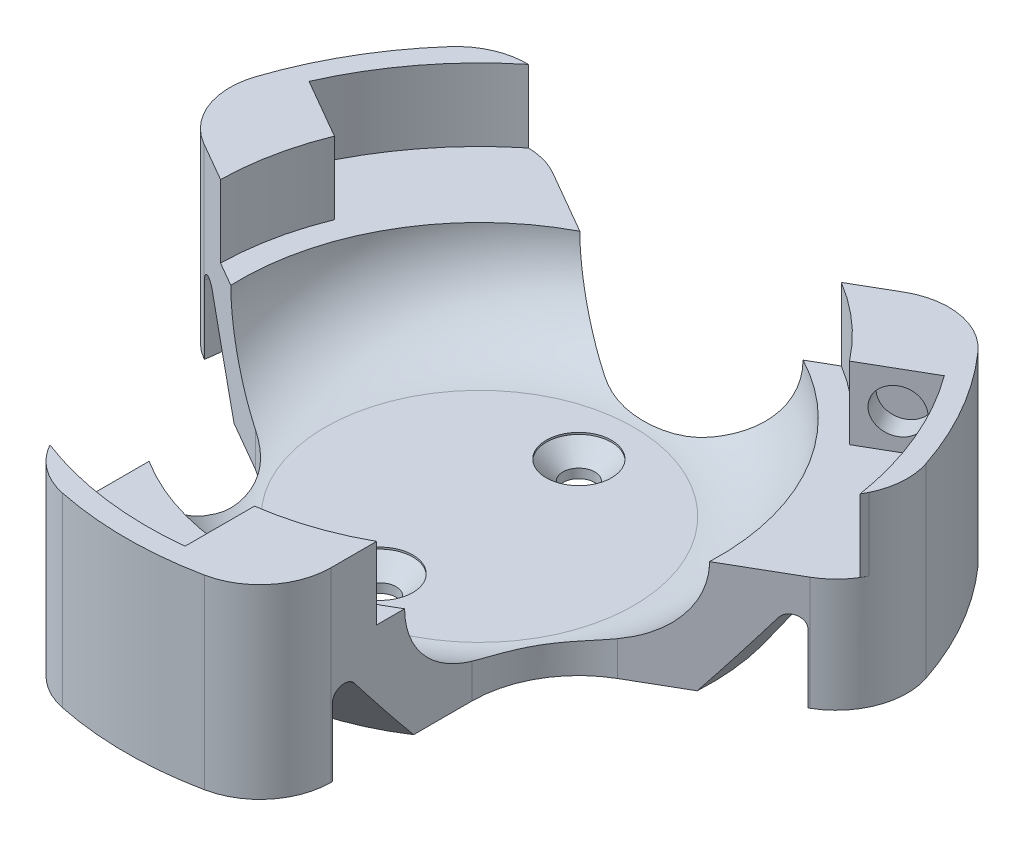
SolidWorks part; units mm, degrees
ref_plane "Front Plane" through (0, 0, 0) normal (0, 0, 1) x (1, 0, 0)
ref_plane "Top Plane" through (0, 0, 0) normal (0, 1, 0) x (1, 0, 0)
ref_plane "Right Plane" through (0, 0, 0) normal (1, 0, 0) x (0, 0, -1)
sketch "Sketch1" plane through (0, 0, 0) normal (0, 1, 0) x (1, 0, 0)
  line L0 (-56, 14) -> (-56, 42)
  line L1 (-28, 14) -> (-28, 42)
  line L3 (-28, 14) -> (-28, 42)
  line L4 (28, 14) -> (28, 42)
  line L5 (28, 14) -> (28, 42)
  line L7 (56, 14) -> (56, 42)
  line L8 (0, 14) -> (0, 42)
  line L9 (56, 14) -> (56, 42)
  line L10 (-56, 42) -> (-56, 70)
  line L11 (-56, 70) -> (-28, 70)
  line L12 (-28, 42) -> (-28, 70)
  line L13 (-28, 42) -> (-28, 70)
  line L15 (0, 70) -> (28, 70)
  line L16 (28, 42) -> (28, 70)
  line L17 (28, 42) -> (28, 70)
  line L18 (28, 70) -> (56, 70)
  line L19 (56, 42) -> (56, 70)
  line L20 (-28, 70) -> (0, 70)
  line L21 (56, 42) -> (56, 70)
  line L23 (0, 42) -> (0, 70)
  line L24 (-56, -14) -> (-56, 14)
  line L25 (-28, -14) -> (-28, 14)
  line L27 (-28, -14) -> (-28, 14)
  line L28 (28, -14) -> (28, 14)
  line L29 (28, -14) -> (28, 14)
  line L31 (56, -14) -> (56, 14)
  line L32 (0, -14) -> (0, 14)
  line L33 (56, -14) -> (56, 14)
  line L34 (-56, 14) -> (-56, 42)
  line L35 (-56, 42) -> (-28, 42)
  line L36 (-28, 14) -> (-28, 42)
  line L37 (-28, 14) -> (-28, 42)
  line L38 (0, 14) -> (0, 42)
  line L39 (0, 42) -> (28, 42)
  line L40 (28, 14) -> (28, 42)
  line L41 (28, 14) -> (28, 42)
  line L42 (28, 42) -> (56, 42)
  line L43 (56, 14) -> (56, 42)
  line L44 (-28, 42) -> (0, 42)
  line L45 (56, 14) -> (56, 42)
  line L46 (0, 14) -> (0, 42)
  line L47 (0, 14) -> (0, 42)
  line L48 (28, -42) -> (56, -42)
  line L49 (0, -42) -> (28, -42)
  line L51 (0, -14) -> (28, -14)
  line L52 (28, -42) -> (28, -14)
  line L53 (28, -42) -> (28, -14)
  line L54 (-28, -42) -> (0, -42)
  line L55 (56, -42) -> (56, -14)
  line L56 (-56, -42) -> (-28, -42)
  line L57 (56, -42) -> (56, -14)
  line L58 (-56, -42) -> (-56, -14)
  line L59 (-56, -14) -> (-28, -14)
  line L60 (28, -14) -> (56, -14)
  line L61 (0, -14) -> (28, -14)
  line L62 (0, -14) -> (0, 14)
  line L63 (0, 14) -> (28, 14)
  line L64 (28, -14) -> (28, 14)
  line L65 (28, -14) -> (28, 14)
  line L66 (28, 14) -> (56, 14)
  line L67 (56, -14) -> (56, 14)
  line L68 (-28, -42) -> (-28, -14)
  line L69 (56, -14) -> (56, 14)
  line L70 (-28, -42) -> (-28, -14)
  line L72 (84, 14) -> (84, 42)
  line L81 (0, -42) -> (0, -14)
  line L82 (-28, -14) -> (0, -14)
  line L83 (-56, -14) -> (-28, -14)
  line L84 (-56, -14) -> (-56, 14)
  line L85 (-56, 14) -> (-28, 14)
  line L86 (-28, -14) -> (-28, 14)
  line L87 (-28, -14) -> (-28, 14)
  line L88 (-28, 14) -> (0, 14)
  line L89 (0, -14) -> (0, 14)
  line L90 (0, -14) -> (0, 14)
  line L92 (0, -42) -> (0, -14)
  line L93 (0, -14) -> (0, 14)
  line L94 (0, 14) -> (0, 42)
  line L95 (0, 42) -> (0, 70)
  dimension "D3" = 3
  dimension "D4" = 2
  dimension "D5" = 3
  dimension "D6" = 2
sketch "Sketch2" plane through (0, 0, 0) normal (0, 1, 0) x (1, 0, 0)
  circle A0 centre (0, 0) radius 33.75
  circle A1 centre (0, 0) radius 49.75
  dimension "D1" = 67.5
  dimension "D2" = 16
extrude "Boss-Extrude1" add sketch "Sketch2" along normal blind 12
sketch "Sketch4" plane through (0, 0, 0) normal (0, 0, 1) x (1, 0, 0)
  line L2 (49.75, 12) -> (-49.75, 12) construction
  line L3 (-49.75, 0) -> (49.75, 0) construction
  line L4 (33.75, 12) -> (33.75, 0)
  line L5 (33.75, 0) -> (21.75, 0)
  ellipse E0 centre (21.75, 12) end of major axis (21.75, 0) minor radius 12 (21.75, 0) -> (33.75, 12) ccw
  dimension "D1" = 12
revolve "Revolve5" add sketch "Sketch4" angle 360 about axis through (0, 12, 0) along (0, -1, 0)
sketch "Sketch5" plane through (0, 0, 0) normal (0, -1, 0) x (1, 0, 0)
  circle A0 centre (0, 0) radius 49.75
  circle A1 centre (0, 0) radius 49.75 construction
extrude "Boss-Extrude2" add sketch "Sketch5" along normal blind 4
sketch "Sketch6" plane through (0, -4, 0) normal (0, -1, 0) x (1, 0, 0)
  line L0 (18, 10.3923) -> (18, 58.2838)
  line L2 (-18, 10.3923) -> (-18, 58.2838)
  line L3 (0, -20.7846) -> (41.4752, -44.7304)
  line L4 (18, 10.3923) -> (59.4752, -13.5534)
  line L6 (0, -20.7846) -> (-41.4752, -44.7304)
  line L7 (-18, 10.3923) -> (-59.4752, -13.5534)
  arc A1 (-18, 58.2838) -> (-59.4752, -13.5534) centre (0, 0) ccw
  arc A2 (59.4752, -13.5534) -> (18, 58.2838) centre (0, 0) ccw
  arc A3 (-41.4752, -44.7304) -> (41.4752, -44.7304) centre (0, 0) ccw
  dimension "D1" = 3
extrude "Cut-Extrude1" cut sketch "Sketch6" against normal through all
sketch "Sketch9" plane through (0, 0, 0) normal (0, 1, 0) x (1, 0, 0)
  circle A0 centre (0, -14) radius 4.6
  circle A1 centre (0, 14) radius 4.6
  dimension "D1" = 9.2
  dimension "D2" = 9.2
extrude "Cut-Extrude2" cut sketch "Sketch9" along normal blind 20 and the other way blind 0.25
fillet "Fillet1" radius 15 3 edges at (0, -2, -20.7846) (-18, -2, 10.3923) (18, -2, 10.3923)
fillet "Fillet2" radius 10 6 edges at (-31.1659, 4, -38.7782) (-49.1659, 4, -7.6013) (18, 4, 46.3795) (-18, 4, 46.3795) (49.1659, 4, -7.6013) (31.1659, 4, -38.7782)
hole_wizard "CSK for M4 Flat Head Machine Screw1" positions "Sketch19" profile "Sketch18" countersink size "M4" standard "ANSI Metric" end condition through all
sketch "Sketch19" plane through (0, -0.25, 0) normal (0, 1, 0) x (1, 0, 0)
  point P0 (0, 14)
  point P3 (0, -14)
sketch "Sketch18" plane through (0, -0.25, -14) normal (1, 0, 0) x (0, 0, 1)
  line L0 (0, 0) -> (0, 3.75)
  line L1 (0, 3.75) -> (2.25, 3.75)
  line L2 (2.25, 3.75) -> (2.25, 2.45)
  line L3 (2.25, 2.45) -> (4.7, 0)
  line L5 (4.7, 0) -> (0, 0)
  line L6 (-2.25, 2.45) -> (-4.7, 0) construction
  line L11 (0, -6.35) -> (0, 107.95) construction
  dimension "Thru Hole Dia." = 4.5
  dimension "Thru Hole Depth" = 3.75
  dimension "Near C'Sink Dia." = 9.4
  dimension "Near C'Sink Angle" = 90
sketch "Sketch20" plane through (0, 12, 0) normal (0, 1, 0) x (1, 0, 0)
  line L0 (-43.0848, 24.875) -> (0, 0) construction
  line L1 (-42.8822, 18.8691) -> (-34.4182, 13.9824)
  line L2 (-42.7201, 3.8799) -> (-33.7244, -1.3138) construction
  line L3 (-42.7201, 3.8799) -> (-37.1441, 0.6606)
  line L4 (-30.4035, 36.3731) -> (-29.5023, 36.3942)
  arc A0 (-34.4182, 13.9824) -> (-37.1441, 0.6606) centre (0, 0) ccw
  arc A1 (-29.5023, 36.3942) -> (-42.8822, 18.8691) centre (0, 0) ccw
  arc A2 (-15.7244, 29.8631) -> (-33.7244, -1.3138) centre (0, 0) ccw construction
  arc A3 (-37.1969, 33.0372) -> (-47.2095, 15.6949) centre (0, 0) ccw construction
  arc A4 (-24.7201, 35.0568) -> (-37.1969, 33.0372) centre (-29.7201, 26.3965) ccw construction
  arc A5 (-47.2095, 15.6949) -> (-42.7201, 3.8799) centre (-37.7201, 12.5401) ccw construction
  arc A6 (-30.4035, 36.3731) -> (-37.1969, 33.0372) centre (-29.7201, 26.3965) ccw
  arc A7 (-37.1969, 33.0372) -> (-47.2095, 15.6949) centre (0, 0) ccw
  arc A8 (-47.2095, 15.6949) -> (-42.7201, 3.8799) centre (-37.7201, 12.5401) ccw
  dimension "D1" = 3.4
  dimension "D2" = 13.1
  dimension "D3" = 5.1
extrude "Boss-Extrude3" add sketch "Sketch20" along normal blind 10.2
sketch "Sketch21" plane through (-2.55, 0, 4.4167) normal (0.5, 0, -0.866) x (-0.866, 0, -0.5)
  line L0 (36.7983, 22.2) -> (36.7983, 12) construction
  line L1 (36.7983, 12) -> (46.5716, 12) construction
  circle A0 centre (41.7983, 17) radius 3.1
  dimension "D1" = 6.2
  dimension "D2" = 5
  dimension "D3" = 5
extrude "Cut-Extrude3" cut sketch "Sketch21" against normal blind 3.1
pattern_circular "CirPattern1" count 3 over 360 about axis through (0, 0, 0) along (0, 1, 0) of "Cut-Extrude3", "Boss-Extrude3"
ref_plane "Plane1" through (0, 0, 0) normal (-0.5, 0, 0.866) x (0.866, 0, 0.5)
sketch "Sketch23" plane through (0, 0, 0) normal (-0.5, 0, 0.866) x (0.866, 0, 0.5)
  line L0 (-42.6814, -4) -> (-42.6814, 10.4433)
  line L1 (-48.732, -4) -> (-38.9366, -4) construction
  line L2 (-42.6814, 10.4433) -> (-32.6814, -4)
  line L3 (-38.9366, -4) -> (-19.0526, -4) construction
  line L4 (-32.6814, -4) -> (-42.6814, -4)
  dimension "D2" = 10
revolve "Cut-Revolve1" cut sketch "Sketch23" angle 360
fillet "Fillet3" radius 1.5 3 edges at (0, 10.4433, 42.6814) (-36.9632, 10.4433, -21.3407) (36.9632, 10.4433, -21.3407)
